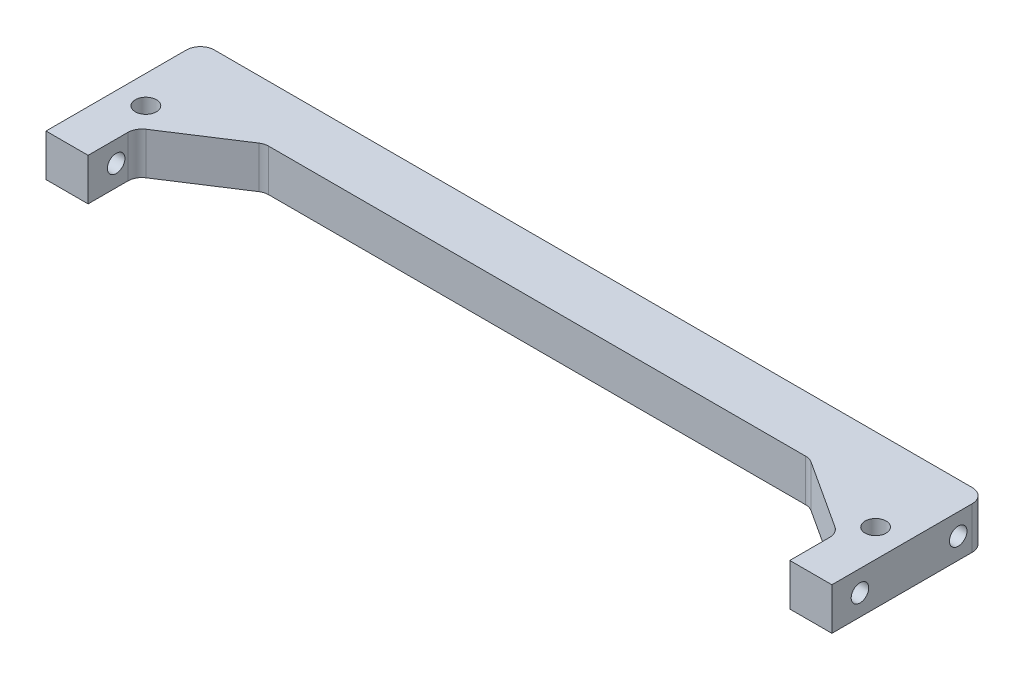
SolidWorks part; units mm, degrees
ref_plane "Front Plane" through (0, 0, 0) normal (0, 0, 1) x (1, 0, 0)
ref_plane "Top Plane" through (0, 0, 0) normal (0, 1, 0) x (1, 0, 0)
ref_plane "Right Plane" through (0, 0, 0) normal (1, 0, 0) x (0, 0, -1)
sketch "Sketch1" plane through (0, 0, 0) normal (0, 1, 0) x (1, 0, 0)
  line L1 (0, -22) -> (-56, -22)
  line L2 (-56, -22) -> (-56, -44)
  line L3 (-50, -37.2398) -> (-38.8516, -30)
  line L4 (0, -30) -> (0, -22)
  line L5 (0, -30) -> (-38.8516, -30)
  line L6 (-56, -44) -> (-50, -44)
  line L7 (-51.9976, -33.7676) -> (-63.9796, -15.3169) construction
  line L8 (-50, -44) -> (-50, -37.2398)
  line L9 (0, 0) -> (-85, 0) construction
  line L10 (-43.8406, 43.8406) -> (0, 0) construction
  line L11 (-51.9976, -33.7676) -> (0, 0) construction
  line L24 (-54.4746, -32.0752) -> (-40.5, -23) construction
  line L25 (-50, 65) -> (-20, 80) construction
  line L26 (-20, 80) -> (0, 80) construction
  line L27 (0, 80) -> (0, 4) construction
  line L28 (0, 4) -> (-50, 4) construction
  line L29 (-50, 65) -> (-50, 4) construction
  circle A0 centre (0, 0) radius 85 construction
  circle A1 centre (-51.9976, -33.7676) radius 3 construction
  circle A2 centre (-51.9976, -33.7676) radius 1.5
  circle A4 centre (-63.9796, -15.3169) radius 1.5 construction
  dimension "D7" = 6
  dimension "D17" = 170
  dimension "D6" = 6
  dimension "D13" = 3
  dimension "D2" = 30
  dimension "D4" = 4
  dimension "D5" = 2.7685
  dimension "D8" = 62
  dimension "D9" = 56
  dimension "D10" = 22
  dimension "D11" = 8
  dimension "D12" = 22
  dimension "D14" = 45
  dimension "D15" = 33
  dimension "D29" = 50
  dimension "D30" = 30
  dimension "D31" = 15
  dimension "D32" = 80
  dimension "D33" = 76
extrude "Boss-Extrude1" add sketch "Sketch1" along normal blind 6
fillet "Fillet1" radius 2 3 edges at (-56, 3, 22) (-50, 3, 37.2398) (-38.8516, 3, 30)
hole_wizard "Tap Drill for M3 Tap1" positions "Sketch3" profile "Sketch2" hole size "M3" standard "ISO"
sketch "Sketch3" plane through (-56, 0, 0) normal (-1, 0, 0) x (0, 0, 1)
  line L0 (44, 6) -> (44, 0) construction
  line L1 (24, 0) -> (44, 0) construction
  point P0 (26, 3)
  point P2 (40, 3)
  dimension "D1" = 4
  dimension "D2" = 14
  dimension "D3" = 3
sketch "Sketch2" plane through (-56, 3, 26) normal (0, 1, 0) x (0, 0, 1)
  line L0 (0, 0) -> (0, 10.7511)
  line L1 (0, 10.7511) -> (1.25, 10)
  line L2 (1.25, 10) -> (1.25, 0)
  line L5 (1.25, 0) -> (0, 0)
  line L10 (0, 10.7511) -> (-1.25, 10) construction
  line L11 (0, -6.35) -> (0, 107.95) construction
  dimension "Hole Dia." = 2.5
  dimension "Hole Depth" = 10
  dimension "Drill Angle" = 118
mirror "Mirror1" about plane through (0, 6, 30) normal (-1, 0, 0) of "Tap Drill for M3 Tap1", "Fillet1", "Boss-Extrude1"
